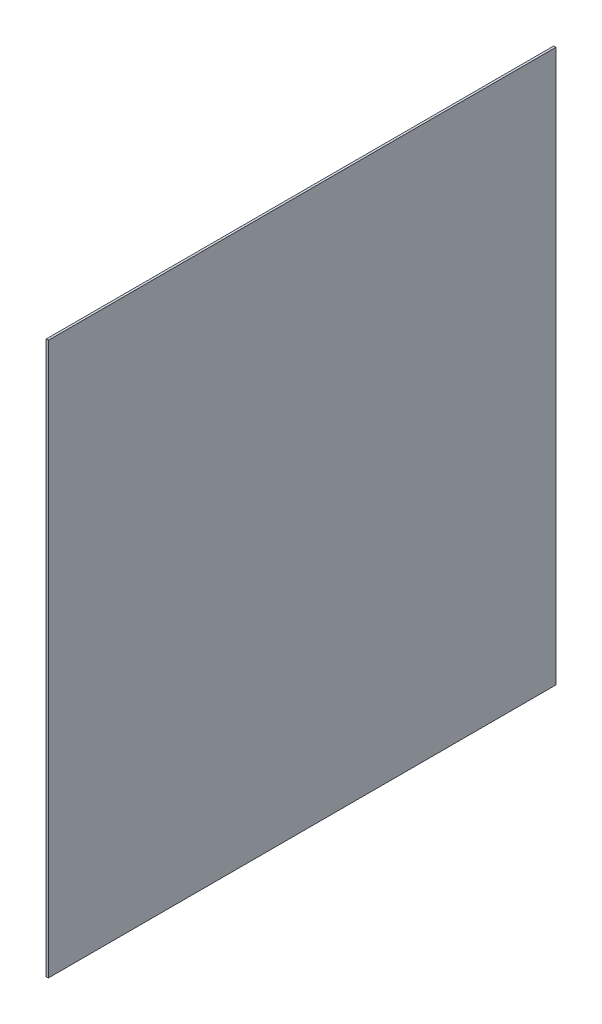
SolidWorks part; units mm, degrees
material "AISI 1020"
ref_plane "Płaszczyzna XY" through (0, 0, 0) normal (0, 0, 1) x (1, 0, 0)
ref_plane "Płaszczyzna XZ" through (0, 0, 0) normal (0, 1, 0) x (1, 0, 0)
ref_plane "Płaszczyzna YZ" through (0, 0, 0) normal (1, 0, 0) x (0, 0, -1)
ref_axis "Oś1" through (650, -200, 440) along (0, 1, 0)
ref_plane "Płaszczyzna1" through (662.5, 0, 0) normal (1, 0, 0) x (0, 0, -1)
sketch "Szkic1" plane through (662.5, 0, 0) normal (1, 0, 0) x (0, 0, -1)
  line L0 (-427.5, 200) -> (-452.5, 200) construction
  line L1 (-452.5, -200) -> (-427.5, -200) construction
  line L2 (-427.5, 200) -> (-452.5, 200) construction
  line L3 (-452.5, -200) -> (-427.5, -200) construction
  line L4 (-440, -200) -> (-440, 200) construction
  line L5 (-440, -185) -> (-100, -185)
  line L6 (-100, -185) -> (-100, 185)
  line L7 (-100, 185) -> (-440, 185)
  line L8 (-440, 185) -> (-440, -185)
  point P9 (-440, 0)
  dimension "D1" = 185
  dimension "D2" = 185
  dimension "D3" = 340
extrude "Dodanie-wyciągnięcie1" add sketch "Szkic1" along normal blind 1.5
